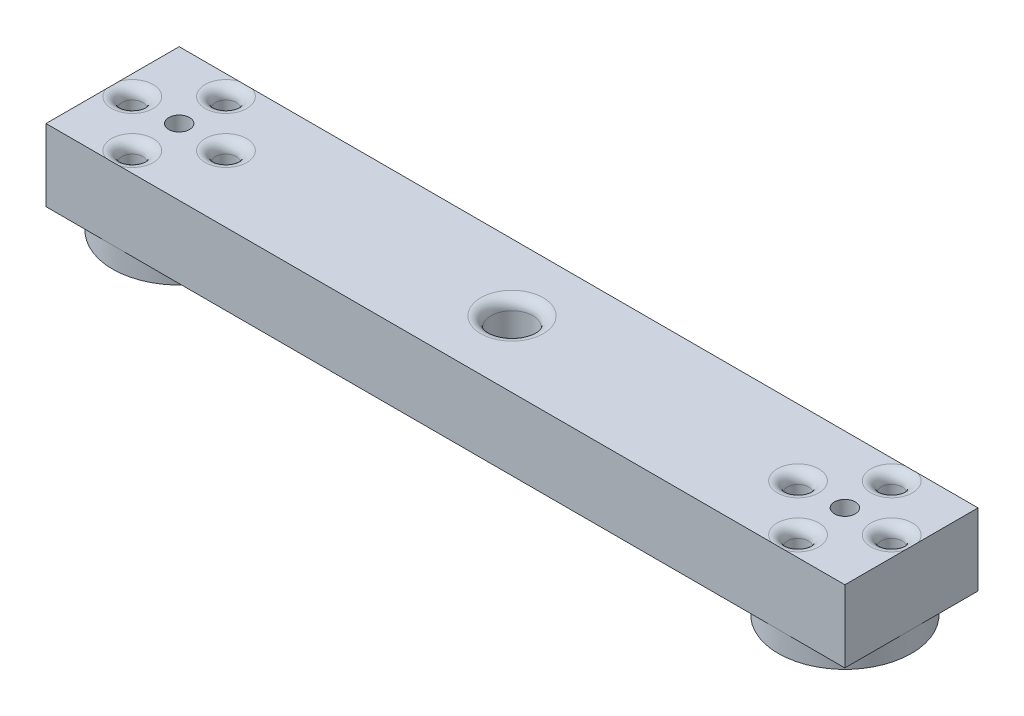
SolidWorks part; units mm, degrees
material "6061-O (SS)"
ref_plane "Front Plane" through (0, 0, 0) normal (0, 0, 1) x (1, 0, 0)
ref_plane "Top Plane" through (0, 0, 0) normal (0, 1, 0) x (1, 0, 0)
ref_plane "Right Plane" through (0, 0, 0) normal (1, 0, 0) x (0, 0, -1)
sketch "Sketch1" plane through (0, 0, 0) normal (0, 1, 0) x (1, 0, 0)
  line L0 (121.92, 0) -> (121.92, 100.0373) construction
  line L1 (0, 0) -> (243.84, 0)
  line L2 (0, 0) -> (0, 40.64)
  line L3 (0, 40.64) -> (243.84, 40.64)
  line L4 (243.84, 0) -> (243.84, 40.64)
  line L5 (0, 20.32) -> (324.8165, 20.32) construction
  circle A0 centre (20.32, 20.32) radius 3.175
  circle A1 centre (20.32, 20.32) radius 14.2875 construction
  circle A2 centre (34.6075, 20.32) radius 3.175
  circle A3 centre (20.32, 6.0325) radius 3.175
  circle A4 centre (6.0325, 20.32) radius 3.175
  circle A5 centre (20.32, 34.6075) radius 3.175
  circle A6 centre (223.52, 34.6075) radius 3.175
  circle A7 centre (237.8075, 20.32) radius 3.175
  circle A8 centre (223.52, 6.0325) radius 3.175
  circle A9 centre (209.2325, 20.32) radius 3.175
  circle A10 centre (223.52, 20.32) radius 3.175
  circle A11 centre (121.92, 20.32) radius 6.35
  dimension "D4" = 6.35
  dimension "D5" = 28.575
  dimension "D6" = 6.35
  dimension "D8" = 12.7
  dimension "D1" = 40.64
  dimension "D2" = 243.84
  dimension "D3" = 20.32
  dimension "D7" = 4
extrude "Boss-Extrude1" add sketch "Sketch1" along normal blind 21.9882
sketch "Sketch2" plane through (0, 0, 0) normal (0, -1, 0) x (1, 0, 0)
  circle A0 centre (20.32, -20.32) radius 20.32
  circle A1 centre (223.52, -20.32) radius 20.32
  circle A2 centre (223.52, -6.0325) radius 3.175 construction
  circle A3 centre (237.8075, -20.32) radius 3.175 construction
  circle A4 centre (223.52, -20.32) radius 3.175 construction
  circle A5 centre (209.2325, -20.32) radius 3.175 construction
  circle A6 centre (223.52, -34.6075) radius 3.175 construction
  circle A7 centre (20.32, -34.6075) radius 3.175 construction
  circle A8 centre (6.0325, -20.32) radius 3.175 construction
  circle A9 centre (20.32, -20.32) radius 3.175 construction
  circle A10 centre (20.32, -6.0325) radius 3.175 construction
  circle A11 centre (34.6075, -20.32) radius 3.175 construction
  circle A12 centre (223.52, -6.0325) radius 3.175
  circle A13 centre (237.8075, -20.32) radius 3.175
  circle A14 centre (223.52, -20.32) radius 3.175
  circle A15 centre (209.2325, -20.32) radius 3.175
  circle A16 centre (223.52, -34.6075) radius 3.175
  circle A17 centre (20.32, -34.6075) radius 3.175
  circle A18 centre (6.0325, -20.32) radius 3.175
  circle A19 centre (20.32, -20.32) radius 3.175
  circle A20 centre (20.32, -6.0325) radius 3.175
  circle A21 centre (34.6075, -20.32) radius 3.175
  dimension "D1" = 40.64
extrude "Boss-Extrude2" add sketch "Sketch2" along normal blind 6.35
fillet "Fillet2" radius 3.175 18 edges at (121.92, 0, -13.97) (121.92, 21.9882, -13.97) (223.52, -6.35, -37.7825) (223.52, 21.9882, -37.7825) (237.8075, -6.35, -23.495) (237.8075, 21.9882, -23.495) (223.52, -6.35, -9.2075) (223.52, 21.9882, -9.2075) (209.2325, -6.35, -23.495) (209.2325, 21.9882, -23.495) (6.0325, -6.35, -23.495) (6.0325, 21.9882, -17.145) (20.32, -6.35, -37.7825) (20.32, 21.9882, -31.4325) (34.6075, -6.35, -23.495) (34.6075, 21.9882, -17.145) (20.32, -6.35, -9.2075) (20.32, 21.9882, -2.8575)
equation "\"C2CD\"= 8'inches, center to center distance"
equation "\"Dflange\"= 1.6'inches, flange diameter"
equation "\"Sy\"= 62.05'MPa, yield strength"
equation "\"Fs\"= 4'factor of safety"
equation "\"E\"= 69'GPa, elastic modulus"
equation "\"W\"= 2'kN"
equation "\"c2cmet\"= ( \"C2CD\" / 39.37 )'center distance meters"
equation "\"Dmet\"= ( \"Dflange\" / 39.37 )'flange diameter meters"
equation "\"height\"= sqr ( ( 3 * \"W\" * \"c2cmet\" ) / ( 1000 * 4 * \"Dmet\" * ( \"Sy\" / \"Fs\" ) ) )'minimum height, meters"
equation "\"highimp\"= \"height\" * 39.37'height, inches"
equation "\"screwD\"= 0.25'screw hole diameter, inches"
equation "\"D1@Sketch1\"= \"Dflange\""
equation "\"D2@Sketch1\"=(\"C2CD\" + \"Dflange\")"
equation "\"D3@Sketch1\"=\"Dflange\" / 2"
equation "\"D4@Sketch1\"=\"screwD\""
equation "\"flangeD\"= 1.125'flange mount diameter"
equation "\"D5@Sketch1\"= \"flangeD\""
equation "\"D6@Sketch1\"= \"screwD\""
equation "\"specD\"= 0.5'diameter of specimen hole"
equation "\"D8@Sketch1\"=\"specD\""
equation "\"D1@Boss-Extrude1\"=\"highimp\""
equation "\"D1@Sketch2\"=\"Dflange\""
